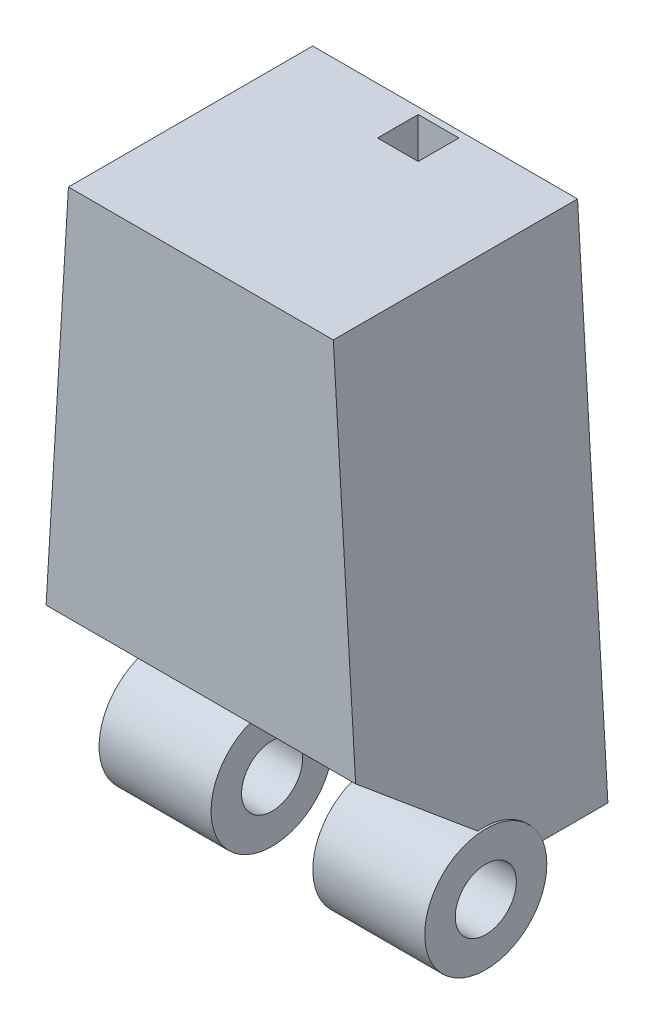
SolidWorks part; units mm, degrees
ref_plane "Front Plane" through (0, 0, 0) normal (0, 0, 1) x (1, 0, 0)
ref_plane "Top Plane" through (0, 0, 0) normal (0, 1, 0) x (1, 0, 0)
ref_plane "Right Plane" through (0, 0, 0) normal (1, 0, 0) x (0, 0, -1)
sketch "Sketch1" plane through (0, 0, 0) normal (0, 0, 1) x (1, 0, 0)
  line L0 (-56.5743, 0) -> (-40.5743, 0)
  line L2 (-56.5743, 0) -> (-55.0819, 24.9554)
  line L3 (-40.5743, 0) -> (-42.0666, 24.9554)
  arc A0 (-42.0666, 24.9554) -> (-55.0819, 24.9554) centre (-48.5743, 24.9554) ccw
extrude "Boss-Extrude1" add sketch "Sketch1" along normal blind 12
sketch "Sketch2" plane through (0, 0, 12) normal (0, 0, 1) x (1, 0, 0)
  line L0 (-40.5743, 0) -> (-56.5743, 0)
  line L1 (-48.5743, 0) -> (-48.5743, 29.5391)
ref_plane "Plane1" through (-48.5743, 0, 0) normal (1, 0, 0) x (0, 0, -1)
sketch "Sketch3" plane through (-48.5743, 0, 0) normal (1, 0, 0) x (0, 0, -1)
  line L0 (0, 0) -> (-4, 0)
  line L1 (-12, 0) -> (0, 0) construction
  line L2 (-4, 0) -> (-12, 6.614)
  line L3 (-12, 0) -> (-12, 24.9554) construction
  line L4 (-12, 6.614) -> (-12, 0)
  line L5 (-12, 0) -> (-4, 0)
extrude "Cut-Extrude1" cut sketch "Sketch3" against normal through all both and the other way through all contours L4 L5 L2 region at (-48.5743, 2.2047, 9.3333)
sketch "Sketch6" plane through (-48.5743, 0, 0) normal (1, 0, 0) x (0, 0, -1)
  line L1 (0, 0) -> (-12, 0)
  line L2 (-6, 0) -> (-6, -1.1)
  circle A0 centre (-6, -1.1) radius 1.5
  circle A1 centre (-6, -1.1) radius 3
extrude "Boss-Extrude2" add sketch "Sketch6" along normal mid plane 16 contours L1 A1 A0 | L1 A1 A0 region at (-48.5743, -0.5537, 3.1241) region at (-48.5743, 0.8343, 6)
extrude "Cut-Extrude2" cut sketch "Sketch6<3>" against normal mid plane 5 contours L1 A1 A0 | L1 A1 A0 region at (-48.5743, -0.5537, 3.1241) region at (-48.5743, 0.8343, 6)
sketch "Sketch6<3>" plane through (-48.5743, 0, 0) normal (1, 0, 0) x (0, 0, -1) same geometry as "Sketch6"
sketch "Sketch7" plane through (-48.5743, 0, 0) normal (1, 0, 0) x (0, 0, -1)
  line L0 (-7.1617, 2.6139) -> (-11.0152, 5.7998)
  line L1 (-6.2821, 1.8867) -> (-12, 6.614) construction
  line L2 (-7.1617, 2.6139) -> (-3.9757, 6.4674)
  line L3 (-3.9757, 6.4674) -> (-7.8293, 9.6534)
  line L4 (-7.8293, 9.6534) -> (-11.0152, 5.7998)
  line L5 (-12, 6.614) -> (-6.2821, 1.8867) construction
extrude "Cut-Extrude3" cut sketch "Sketch7" against normal mid plane 10
sketch "Sketch8" plane through (-48.5743, 0, 0) normal (1, 0, 0) x (0, 0, -1)
  circle A0 centre (-7.5481, 6.1771) radius 1.5
extrude "Boss-Extrude3" add sketch "Sketch8" along normal mid plane 11
sketch "Sketch9" plane through (-48.5743, 0, 0) normal (1, 0, 0) x (0, 0, -1)
  line L1 (-12, 31.4631) -> (0, 31.4631)
  line L2 (-12, 31.4631) -> (-12, 24.9554)
  line L3 (-12, 24.9554) -> (0, 24.9554)
  line L4 (0, 31.4631) -> (0, 24.9554)
extrude "Cut-Extrude4" cut sketch "Sketch9" against normal through all both and the other way through all
sketch "Sketch10" plane through (-48.5743, 0, 0) normal (1, 0, 0) x (0, 0, -1)
  line L0 (-0.32, 0) -> (-2.32, 0)
  line L1 (-3.2089, 0) -> (0, 0) construction
  line L2 (-2.32, 0) -> (-2.32, 0.8015)
  line L3 (-0.32, 0.8015) -> (-0.32, 27.3773)
  line L4 (-0.32, 0.8015) -> (-0.32, 0)
  line L5 (-0.32, 27.3773) -> (-2.32, 27.3773)
  line L6 (-2.32, 27.3773) -> (-2.32, 0)
extrude "Cut-Extrude5" cut sketch "Sketch10" against normal mid plane 2 contours L5 L6 L2 L0 L4 L3 region at (-48.5743, 13.6886, 1.32)
